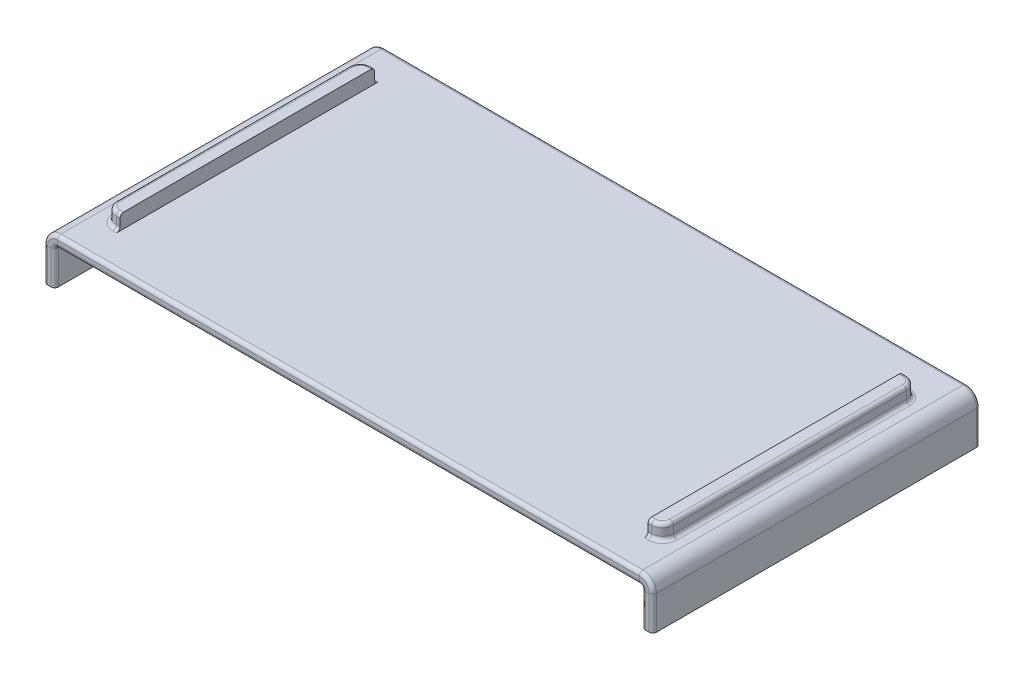
SolidWorks part; units mm, degrees
note: The reader was unsure of these and kept them because the rebuilt part matched: thickness of "Tôle de base pliée1", "Tôle pliée sur arête1", "Tôle pliée sur arête2"; flange length of "Tôle pliée sur arête1", "Tôle pliée sur arête2".
ref_plane "Plan de face" through (0, 0, 0) normal (0, 0, 1) x (1, 0, 0)
ref_plane "Plan de dessus" through (0, 0, 0) normal (0, 1, 0) x (1, 0, 0)
ref_plane "Plan de droite" through (0, 0, 0) normal (1, 0, 0) x (0, 0, -1)
sketch "Esquisse1" plane through (0, 0, 0) normal (0, 1, 0) x (1, 0, 0)
  line L1 (-106.904, 61.8266) -> (53.096, 61.8266)
  line L2 (-106.904, 61.8266) -> (-106.904, -28.1734)
  line L3 (-106.904, -28.1734) -> (53.096, -28.1734)
  line L4 (53.096, 61.8266) -> (53.096, -28.1734)
  dimension "D1" = 90
  dimension "D2" = 160
sheet metal parameters "Tôlerie 1" thickness 3 parameters "D1"=0.7366, "Epaisseur"=3
base flange "Tôle de base pliée1" sketch "Esquisse1" thickness 3 reverse thickness direction yes parameters "D1"=0.7366
edge flange "Tôle pliée sur arête1" sketch "Esquisse5" flange angle 90 flange length 10 flange position bend outside bend radius 0.7366 thickness 3 relief rectangular parameters "D6"=10
sketch "Esquisse5" plane through (53.096, 0, 0) normal (1, 0, 0) x (0, 0, 1)
  line L0 (28.1734, 0) -> (-61.8266, 0) construction
  line L1 (28.1734, 0) -> (-61.8266, 0)
  line L2 (-61.8266, 0) -> (-61.8266, 10)
  line L3 (-61.8266, 10) -> (28.1734, 10)
  line L4 (28.1734, 10) -> (28.1734, 0)
bend "Pli d'arête1" bend radius 0.7366 bend angle 90 parameters "D5"=1
edge flange "Tôle pliée sur arête2" sketch "Esquisse8" flange angle 90 flange length 10 flange position bend outside bend radius 0.7366 thickness 3 relief rectangular parameters "D6"=10
sketch "Esquisse8" plane through (-106.904, 0, 0) normal (-1, 0, 0) x (0, 0, -1)
  line L0 (61.8266, 0) -> (-28.1734, 0) construction
  line L1 (61.8266, 0) -> (-28.1734, 0)
  line L2 (-28.1734, 0) -> (-28.1734, 10)
  line L3 (-28.1734, 10) -> (61.8266, 10)
  line L4 (61.8266, 10) -> (61.8266, 0)
bend "Pli d'arête2" bend radius 0.7366 bend angle 90 parameters "D5"=2
fillet "Congé1" [suppressed] radius 4
sketch "Esquisse9" plane through (0, 3, 0) normal (0, 1, 0) x (1, 0, 0)
  line L0 (-26.904, 61.8266) -> (-26.904, -28.1734) construction
  line L1 (-100.5048, 51.6447) -> (-99.5048, 51.6447)
  line L2 (-103.5048, 48.6447) -> (-103.5048, -15.3553)
  line L3 (-100.5048, -18.3553) -> (-99.5048, -18.3553)
  line L4 (-99.5048, 51.6447) -> (-99.5048, -18.3553)
  line L5 (53.096, 61.8266) -> (-106.904, 61.8266) construction
  line L6 (-106.904, -28.1734) -> (53.096, -28.1734) construction
  line L7 (45.6969, 51.6447) -> (45.6969, -18.3553)
  line L8 (46.6969, -18.3553) -> (45.6969, -18.3553)
  line L9 (49.6969, 48.6447) -> (49.6969, -15.3553)
  line L10 (46.6969, 51.6447) -> (45.6969, 51.6447)
  line L12 (-104.0048, -13.0178) -> (-104.0048, 46.9822) construction
  arc A0 (-103.5048, 48.6447) -> (-100.5048, 51.6447) centre (-100.5048, 48.6447) cw
  arc A1 (-103.5048, -15.3553) -> (-100.5048, -18.3553) centre (-100.5048, -15.3553) ccw
  arc A2 (49.6969, -15.3553) -> (46.6969, -18.3553) centre (46.6969, -15.3553) cw
  arc A3 (49.6969, 48.6447) -> (46.6969, 51.6447) centre (46.6969, 48.6447) ccw
  point P6 (-103.5048, 51.6447)
  point P23 (49.6969, 51.6447)
  dimension "D3" = 3
  dimension "D4" = 3
  dimension "D1" = 4
  dimension "D2" = 70
  dimension "D5" = 0.5
extrude "Extrusion1" add sketch "Esquisse9" along normal blind 4
fillet "Congé2" radius 1 20 edges at (-26.904, 3, -61.8266) (55.7382, 1.9056, -61.8266) (55.7382, 1.9056, 28.1734) (53.6169, -0.2157, -61.8266) (53.6169, -0.2157, 28.1734) (53.8326, -5.3683, 28.1734) (53.8326, -5.3683, -61.8266) (56.8326, -5.3683, 28.1734) (56.8326, -5.3683, -61.8266) (-109.5462, 1.9056, 28.1734) (-109.5462, 1.9056, -61.8266) (-107.4248, -0.2157, 28.1734) (-107.4248, -0.2157, -61.8266) (-26.904, 0, -61.8266) (-107.6406, -5.3683, -61.8266) (-107.6406, -5.3683, 28.1734) (-110.6406, -5.3683, -61.8266) (-110.6406, -5.3683, 28.1734) (-26.904, 0, 28.1734) (-26.904, 3, 28.1734)
fillet "Congé3" radius 1 10 edges at (46.1969, 7, 18.3553) (48.8182, 7, 17.4766) (46.1969, 7, -51.6447) (48.8182, 7, -50.766) (-100.0048, 7, -51.6447) (-102.6261, 7, -50.766) (-100.0048, 7, 18.3553) (-102.6261, 7, 17.4766) (49.6969, 7, -16.6447) (-103.5048, 7, -16.6447)
fillet "Congé4" radius 1 10 edges at (-100.0048, 3, -51.6447) (-102.6261, 3, -50.766) (-100.0048, 3, 18.3553) (-102.6261, 3, 17.4766) (-103.5048, 3, -16.6447) (46.1969, 3, 18.3553) (48.8182, 3, 17.4766) (46.1969, 3, -51.6447) (48.8182, 3, -50.766) (49.6969, 3, -16.6447)
flat pattern "Etat déplié1"
sketch "Lignes de pliage1" plane through (0, 5, 0) normal (0, 1, 0) x (-1, 0, 0)
  line L0 (109.446, 28.1734) -> (109.446, -61.8266) construction
  line L1 (-55.638, -61.8266) -> (-55.638, 28.1734) construction
  line L2 (109.446, 28.1734) -> (109.446, -61.8266) construction
  line L3 (-55.638, -61.8266) -> (-55.638, 28.1734) construction
bend of the flat pattern "Dépliage-<Pli d'arête1>1"
bend of the flat pattern "Dépliage-<Pli d'arête2>1"
scale "Echelle1" [suppressed]
